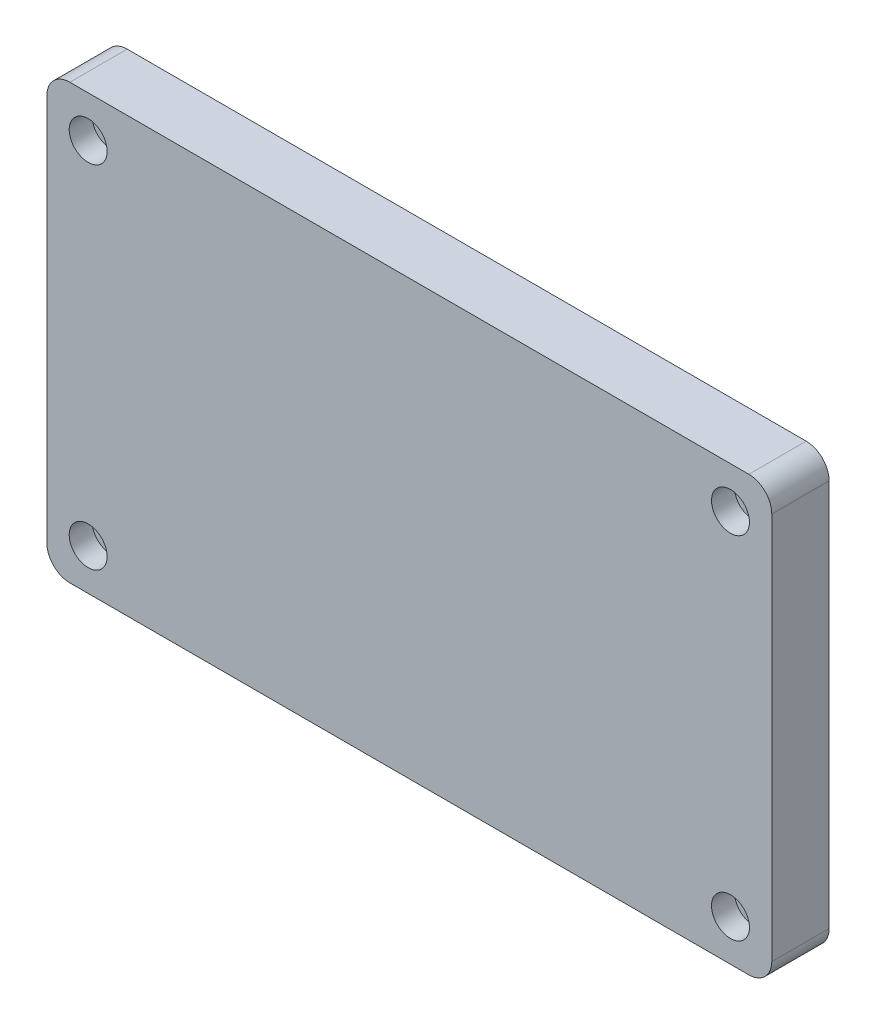
SolidWorks part; units mm, degrees
material "Custom Plastic"
ref_plane "X-Y Datum" through (0, 0, 0) normal (0, 0, 1) x (1, 0, 0)
ref_plane "X-Z Datum" through (0, 0, 0) normal (0, 1, 0) x (1, 0, 0)
ref_plane "Y-Z Datum" through (0, 0, 0) normal (1, 0, 0) x (0, 0, -1)
sketch "Sketch1" plane through (0, 0, 0) normal (0, 0, 1) x (1, 0, 0)
  line L1 (-40.132, -24.003) -> (40.132, -24.003)
  line L2 (-40.132, -24.003) -> (-40.132, 24.003)
  line L3 (-40.132, 24.003) -> (40.132, 24.003)
  line L4 (40.132, -24.003) -> (40.132, 24.003)
  line L5 (-40.132, -24.003) -> (40.132, 24.003) construction
  line L6 (-40.132, 24.003) -> (40.132, -24.003) construction
  line L7 (-35.56, -19.431) -> (35.56, -19.431)
  line L8 (-35.56, -19.431) -> (-35.56, 19.431)
  line L9 (-35.56, 19.431) -> (35.56, 19.431)
  line L10 (35.56, -19.431) -> (35.56, 19.431)
  line L11 (-35.56, -19.431) -> (35.56, 19.431) construction
  line L12 (-35.56, 19.431) -> (35.56, -19.431) construction
  point P0 (0, 0)
  point P6 (0, 0)
  dimension "D1" = 48.006
  dimension "D2" = 80.264
extrude "Boss-Extrude1" add sketch "Sketch1" along normal blind 6.35 contours L7 L10 L9 L8 | L1 L4 L3 L2 L10 L7 L8 L9 region at (-39.1968, 0, 0) region at (0, 0, 0)
sketch "Sketch2" plane through (0, 0, 6.35) normal (0, 0, 1) x (1, 0, 0)
  line L0 (-40.132, -24.003) -> (40.132, 24.003) construction
  line L1 (-35.56, -19.431) -> (35.56, -19.431)
  line L2 (-35.56, -19.431) -> (-35.56, 19.431)
  line L3 (-35.56, 19.431) -> (35.56, 19.431)
  line L4 (35.56, -19.431) -> (35.56, 19.431)
  line L5 (-35.56, -19.431) -> (35.56, 19.431) construction
  line L6 (-35.56, 19.431) -> (35.56, -19.431) construction
  circle A0 centre (-35.56, 19.431) radius 2.1
  circle A1 centre (-35.56, -19.431) radius 2.1
  circle A2 centre (35.56, 19.431) radius 2.1
  circle A3 centre (35.56, -19.431) radius 2.1
  point P9 (0, 0)
extrude "Cut-Extrude2" cut sketch "Sketch2" against normal blind 2.54 contours L3 A0 L2 | L2 A0 L3 | L2 A1 L1 | L1 A1 L2 | L4 A2 L3 | L3 A2 L4 | L1 A3 L4 | L4 A3 L1 region at (-34.6687, -18.5397, 6.35) region at (-35.8571, -19.7281, 6.35) region at (34.6687, -18.5397, 6.35) region at (35.8571, -19.7281, 6.35) region at (-35.8571, 19.7281, 6.35) region at (-34.6687, 18.5397, 6.35) region at (34.6687, 18.5397, 6.35) region at (35.8571, 19.7281, 6.35)
fillet "Fillet1" radius 2.54 4 edges at (40.132, -24.003, 3.175) (40.132, 24.003, 3.175) (-40.132, -24.003, 3.175) (-40.132, 24.003, 3.175)
